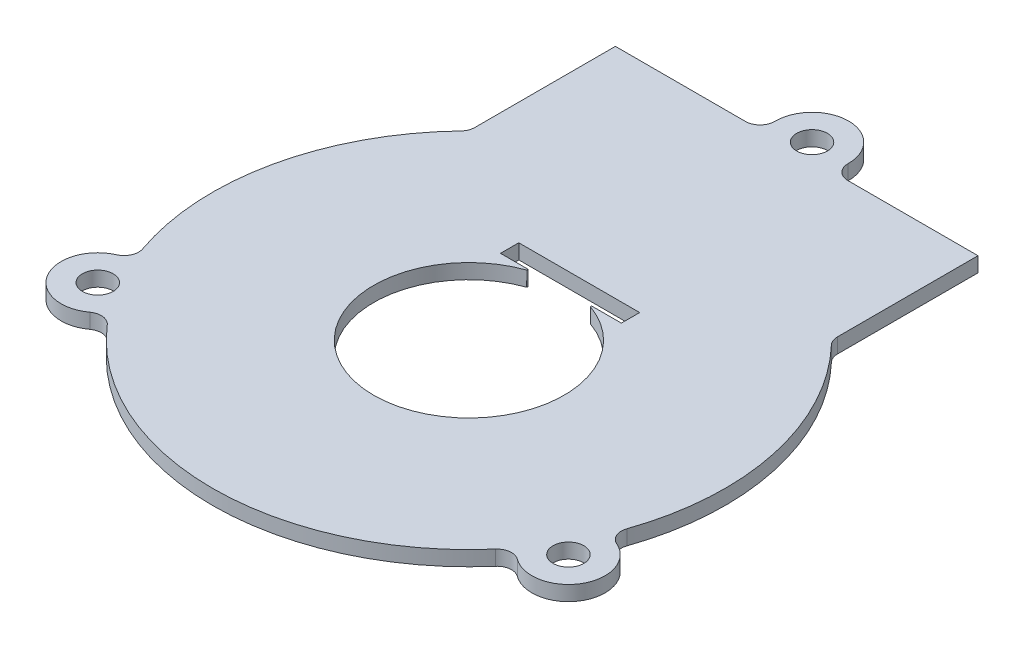
SolidWorks part; units mm, degrees
ref_plane "Front Plane" through (0, 0, 0) normal (0, 0, 1) x (1, 0, 0)
ref_plane "Top Plane" through (0, 0, 0) normal (0, 1, 0) x (1, 0, 0)
ref_plane "Right Plane" through (0, 0, 0) normal (1, 0, 0) x (0, 0, -1)
sketch "Sketch13" plane through (0, 0, 0) normal (0, 1, 0) x (1, 0, 0)
  circle A0 centre (0, 0) radius 35
extrude "Boss-Extrude3" add sketch "Sketch13" along normal blind 2.032
sketch "Sketch14" plane through (0, 2.032, 0) normal (0, 1, 0) x (1, 0, 0)
  line L0 (-24.7478, 24.7497) -> (24.7477, 24.7498)
  line L1 (-24.7478, 24.7497) -> (-24.7479, 44.7452)
  line L2 (24.7477, 24.7498) -> (24.7476, 44.7454)
  line L3 (-24.7479, 44.7452) -> (24.7476, 44.7454)
  line L4 (0, 0) -> (60.4611, -34.8658) construction
  line L5 (0, 0) -> (-56.6044, -32.6614) construction
  line L7 (-3.939, 44.1714) -> (-8.8985, 44.1714)
  line L8 (-3.939, 44.1714) -> (-3.939, 47.547)
  line L9 (-3.939, 47.547) -> (-8.8985, 47.547)
  line L10 (-8.8985, 44.1714) -> (-8.8985, 47.547)
  arc A0 (0, 35) -> (-24.7478, 24.7497) centre (0, 0) ccw construction
  circle A1 centre (0, 0) radius 35 construction
  arc A2 (0, 35) -> (-30.3109, -17.4999) centre (0, 0) ccw construction
  arc A3 (0, 35) -> (30.3118, -17.4984) centre (0, 0) ccw
  arc A4 (0, 35) -> (24.7477, 24.7498) centre (0, 0) ccw construction
  circle A5 centre (32.1365, -18.5413) radius 2.1017
  circle A6 centre (32.1365, -18.5413) radius 4.9951
  circle A7 centre (-32.1465, -18.5162) radius 2.0981
  circle A8 centre (-32.1465, -18.5162) radius 4.9995
extrude "Boss-Extrude4" add sketch "Sketch14" against normal up to surface (2.032 mm away) contours L0 L1 L3 L2 up to face at (0, 0, 35)
sketch "Sketch15" plane through (0, 2.032, 0) normal (0, 1, 0) x (1, 0, 0)
  line L0 (0, 0) -> (0, 62.3966) construction
  line L1 (-0.0001, 44.7453) -> (0, 46.8414) construction
  line L2 (-24.7479, 44.7452) -> (24.7476, 44.7454) construction
  circle A0 centre (0, 46.8414) radius 2.0961
  circle A1 centre (0, 46.8414) radius 4.996
extrude "Boss-Extrude11" add sketch "Sketch15" against normal blind 2.032 contours A1 | A0
extrude "Boss-Extrude12" add sketch "Sketch14<6>" against normal up to surface (2.032 mm away) contours A6 up to face at (0, 0, -29.3038)
sketch "Sketch14<6>" plane through (0, 2.032, 0) normal (0, 1, 0) x (1, 0, 0) same geometry as "Sketch14"
extrude "Boss-Extrude14" add sketch "Sketch14<8>" against normal through all contours L0 A5 region at (32.1365, 2.032, 18.5413)
sketch "Sketch14<8>" plane through (0, 2.032, 0) normal (0, 1, 0) x (1, 0, 0) same geometry as "Sketch14"
hole_wizard "Ø4.2 (4.2) Diameter Hole1" positions "Sketch22" profile "Sketch23" hole size "Ø4.2" standard "ANSI Metric" end condition through all
sketch "Sketch22" plane through (0, 2.032, 0) normal (0, 1, 0) x (1, 0, 0)
  point P0 (32.1248, -18.5356)
sketch "Sketch23" plane through (32.1248, 2.032, 18.5356) normal (1, 0, 0) x (0, 0, 1)
  line L0 (0, 0) -> (0, 2.032)
  line L1 (0, 2.032) -> (2.1, 2.032)
  line L2 (2.1, 2.032) -> (2.1, 0)
  line L5 (2.1, 0) -> (0, 0)
  line L11 (0, -6.35) -> (0, 107.95) construction
  dimension "Thru Hole Dia." = 4.2
  dimension "Thru Hole Depth" = 2.032
extrude "Boss-Extrude15" add sketch "Sketch14<11>" against normal up to surface (2.032 mm away) contours A8 up to face at (32.1248, 0, 20.6356)
sketch "Sketch14<11>" plane through (0, 2.032, 0) normal (0, 1, 0) x (1, 0, 0) same geometry as "Sketch14"
hole_wizard "Ø4.2 (4.2) Diameter Hole2" positions "Sketch26" profile "Sketch27" hole size "Ø4.2" standard "ANSI Metric" end condition through all
sketch "Sketch26" plane through (0, 2.032, 0) normal (0, 1, 0) x (1, 0, 0)
  point P0 (-32.148, -18.5088)
  point P2 (-32.148, -18.5088)
sketch "Sketch27" plane through (-32.148, 2.032, 18.5088) normal (1, 0, 0) x (0, 0, 1)
  line L0 (0, 0) -> (0, 2.032)
  line L1 (0, 2.032) -> (2.1, 2.032)
  line L2 (2.1, 2.032) -> (2.1, 0)
  line L5 (2.1, 0) -> (0, 0)
  line L11 (0, -6.35) -> (0, 107.95) construction
  dimension "Thru Hole Dia." = 4.2
  dimension "Thru Hole Depth" = 2.032
fillet "Fillet4" radius 2 1 edges at (-24.7478, 1.016, -24.7497)
fillet "Fillet6" radius 2 1 edges at (-32.2839, 1.016, 13.5185)
fillet "Fillet7" radius 2 1 edges at (-27.8924, 1.016, 21.1427)
fillet "Fillet8" radius 2 1 edges at (27.8812, 1.016, 21.1574)
fillet "Fillet9" radius 2 1 edges at (32.2715, 1.016, 13.548)
fillet "Fillet10" radius 2 1 edges at (24.7477, 1.016, -24.7498)
fillet "Fillet11" radius 2 1 edges at (4.535, 1.016, -44.7453)
fillet "Fillet12" radius 2 1 edges at (-4.535, 1.016, -44.7453)
sketch "Sketch28" plane through (0, 2.032, 0) normal (0, 1, 0) x (1, 0, 0)
  circle A0 centre (0, 0) radius 5
extrude "Cut-Extrude1" cut sketch "Sketch28" against normal up to surface (2.032 mm away) up to face at (-32.148, 0, 20.6088)
sketch "Sketch29" plane through (0, 2.032, 0) normal (0, 1, 0) x (1, 0, 0)
  circle A0 centre (0, 0) radius 13
extrude "Cut-Extrude2" cut sketch "Sketch29" against normal up to surface (2.032 mm away) contours A0 up to face at (0, 0, 5)
sketch "Sketch30" plane through (0, 2.032, 0) normal (0, 1, 0) x (1, 0, 0)
  line L1 (8.3778, 12.4336) -> (-8.1222, 12.4336)
  line L2 (8.3778, 12.4336) -> (8.3778, 14.9336)
  line L3 (8.3778, 14.9336) -> (-8.1222, 14.9336)
  line L4 (-8.1222, 12.4336) -> (-8.1222, 14.9336)
  dimension "D1" = 16.5
  dimension "D2" = 2.5
extrude "Cut-Extrude5" cut sketch "Sketch30" against normal up to surface (2.032 mm away) contours L2 L1 L4 L3 up to face at (0, 0, 13)
fillet "Fillet17" radius 0.1 2 edges at (3.7955, 1.016, -12.4336) (-3.7955, 1.016, -12.4336)
